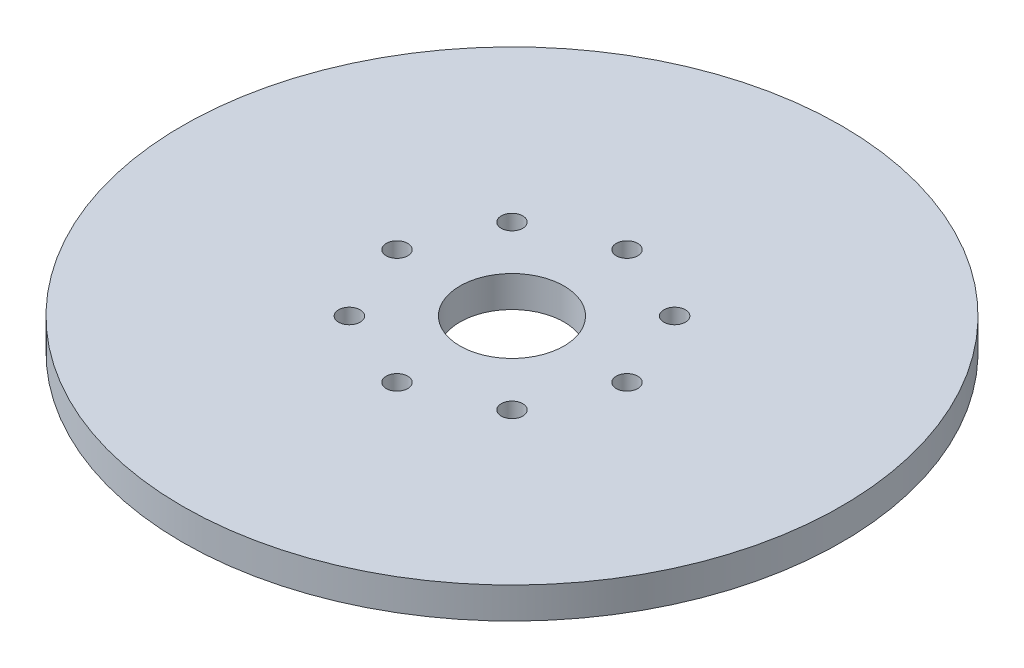
SolidWorks part; units mm, degrees
ref_plane "Front Plane" through (0, 0, 0) normal (0, 0, 1) x (1, 0, 0)
ref_plane "Top Plane" through (0, 0, 0) normal (0, 1, 0) x (1, 0, 0)
ref_plane "Right Plane" through (0, 0, 0) normal (1, 0, 0) x (0, 0, -1)
sketch "Sketch1" plane through (0, 0, 0) normal (0, 1, 0) x (1, 0, 0)
  circle A0 centre (0, 0) radius 95
  dimension "FLANGE_OD" = 190
extrude "Boss-Extrude1" add sketch "Sketch1" along normal blind 9
sketch "Sketch2" plane through (0, 0, 0) normal (0, 1, 0) x (1, 0, 0)
  circle A0 centre (0, 0) radius 15
  dimension "BORE_D" = 30
extrude "Cut-Extrude1" cut sketch "Sketch2" along normal through all
sketch "Sketch3" plane through (0, 9, 0) normal (0, 1, 0) x (1, 0, 0)
  circle A0 centre (0, 0) radius 33.1517 construction
  circle A1 centre (-33.1517, 0) radius 3.1077
  dimension "BOLT_D" = 6.2153
  dimension "BOLT_PCD" = 66.3034
extrude "Cut-Extrude2" cut sketch "Sketch3" against normal blind 7.0454
pattern_circular "CirPattern1" count 8 over 360 about axis through (0, 0, 0) along (0, 1, 0) of "Cut-Extrude2"
